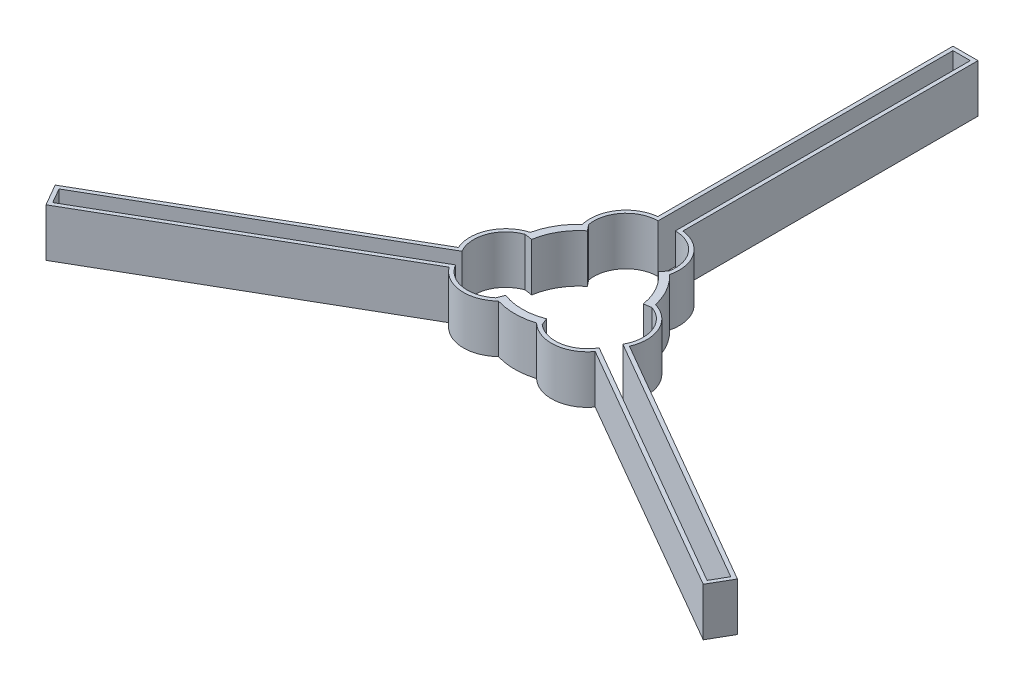
SolidWorks part; units mm, degrees
ref_plane "Front Plane" through (0, 0, 0) normal (0, 0, 1) x (1, 0, 0)
ref_plane "Top Plane" through (0, 0, 0) normal (0, 1, 0) x (1, 0, 0)
ref_plane "Right Plane" through (0, 0, 0) normal (1, 0, 0) x (0, 0, -1)
sketch "Sketch1" plane through (0, 0, 0) normal (0, 1, 0) x (1, 0, 0)
  line L0 (0, 133.3841) -> (0, -45.2268) construction
  line L1 (-53.2552, 0) -> (46.6987, 0) construction
  line L2 (25.0719, -11.3576) -> (104.6668, -57.3117)
  line L3 (104.6668, -57.3117) -> (101.9668, -61.9883)
  line L4 (-2.7, 27.3917) -> (-2.7, 119.3)
  line L5 (-2.7, 119.3) -> (2.7, 119.3)
  line L6 (-2.7, 78.9073) -> (-2.7, 10.5714) construction
  line L7 (-3.9, 120.5) -> (-3.9, 28.5272)
  line L8 (-3.9, 120.5) -> (0, 120.5)
  line L9 (-12.5353, 15.5842) -> (0, 0) construction
  line L10 (106.3061, -56.8725) -> (26.6553, -10.8861)
  line L11 (106.3061, -56.8725) -> (104.3561, -60.25)
  line L12 (19.7639, 3.0638) -> (17.3923, 2.6961)
  line L13 (7.2286, -18.648) -> (6.3612, -16.4102)
  line L14 (22.3719, -16.0341) -> (101.9668, -61.9883)
  line L15 (102.4061, -63.6275) -> (22.7553, -17.6411)
  line L16 (102.4061, -63.6275) -> (104.3561, -60.25)
  line L17 (115.514, -66.692) -> (-39.1675, 22.6134) construction
  line L18 (26.6276, 46.1204) -> (-23.3493, -40.4422) construction
  line L19 (69.6857, -37.1154) -> (10.5051, -2.9474) construction
  line L20 (19.7639, 3.0638) -> (0, 0) construction
  line L21 (-22.3719, -16.0341) -> (-101.9668, -61.9883)
  line L22 (-101.9668, -61.9883) -> (-104.6668, -57.3117)
  line L23 (-102.4061, -63.6275) -> (-22.7553, -17.6411)
  line L24 (-12.5353, 15.5842) -> (-11.0311, 13.7141)
  line L25 (12.5353, 15.5842) -> (11.0311, 13.7141)
  line L26 (2.7, 27.3917) -> (2.7, 119.3)
  line L27 (3.9, 120.5) -> (3.9, 28.5272)
  line L28 (3.9, 120.5) -> (0, 120.5)
  line L29 (-102.4061, -63.6275) -> (-104.3561, -60.25)
  line L30 (-7.2286, -18.648) -> (-6.3612, -16.4102)
  line L31 (-19.7639, 3.0638) -> (-17.3923, 2.6961)
  line L32 (-25.0719, -11.3576) -> (-104.6668, -57.3117)
  line L33 (-106.3061, -56.8725) -> (-26.6553, -10.8861)
  line L34 (-106.3061, -56.8725) -> (-104.3561, -60.25)
  line L35 (-115.514, -66.692) -> (39.1675, 22.6134) construction
  line L36 (26.6276, -46.1204) -> (-23.3493, 40.4422) construction
  line L37 (-66.9857, -41.7919) -> (-7.8051, -7.624) construction
  line L38 (-7.2286, -18.648) -> (0, 0) construction
  circle A0 centre (0, 0) radius 17.6
  circle A1 centre (0, 0) radius 20
  arc A2 (-2.7, 27.3917) -> (-12.5353, 15.5842) centre (-2.7, 17.3917) ccw
  arc A3 (-3.9, 28.5272) -> (-13.5698, 14.6922) centre (-2.7, 17.3917) ccw
  arc A4 (3.9, 28.5272) -> (13.5698, 14.6922) centre (2.7, 17.3917) cw
  arc A5 (2.7, 27.3917) -> (12.5353, 15.5842) centre (2.7, 17.3917) cw
  arc A6 (25.0719, -11.3576) -> (19.7639, 3.0638) centre (16.4116, -6.3576) ccw
  arc A7 (26.6553, -10.8861) -> (19.5087, 4.4057) centre (16.4116, -6.3576) ccw
  arc A8 (22.7553, -17.6411) -> (5.9389, -19.0979) centre (13.7116, -11.0341) cw
  arc A9 (22.3719, -16.0341) -> (7.2286, -18.648) centre (13.7116, -11.0341) cw
  arc A10 (-22.3719, -16.0341) -> (-7.2286, -18.648) centre (-13.7116, -11.0341) ccw
  arc A11 (-22.7553, -17.6411) -> (-5.9389, -19.0979) centre (-13.7116, -11.0341) ccw
  arc A12 (-26.6553, -10.8861) -> (-19.5087, 4.4057) centre (-16.4116, -6.3576) cw
  arc A13 (-25.0719, -11.3576) -> (-19.7639, 3.0638) centre (-16.4116, -6.3576) cw
  point P16 (-1.95, 120.5)
  point P19 (0, 20)
  point P30 (17.3205, -10)
  point P34 (0, 0)
  point P43 (0, 0)
  point P56 (0, 119.3)
  point P58 (103.3168, -59.65)
  point P69 (-17.3205, -10)
  point P73 (0, 0)
  point P84 (-103.3168, -59.65)
  point P85 (0, 0)
  dimension "D1" = 35.2
  dimension "D2" = 40
  dimension "D6" = 10
  dimension "D8" = 1.2
  dimension "D3" = 3
  dimension "D5" = 2.7
  dimension "D7" = 1.2
  dimension "D9" = 1.2
  dimension "D10" = 99.3
extrude "Boss-Extrude1" add sketch "Sketch1" along normal blind 15 contours L26 A5 A1 A4 L27 L28 L8 L7 A3 A2 L4 L5 | L24 A1 L31 A0 | L32 A13 A1 A12 L33 L34 L29 L23 A11 A10 L21 L22 | L12 A1 L25 A0 | L30 A1 L13 A0 | L14 A9 A1 A8 L15 L16 L11 L10 A7 A6 L2 L3 region at (25.9099, 0, 2.8616) region at (15.9343, 0, -9.1997) region at (0, 0, 18.3994) region at (13.7746, 0, -15.9755) region at (-15.9343, 0, -9.1997) region at (-14.6678, 0, 22.0715)
